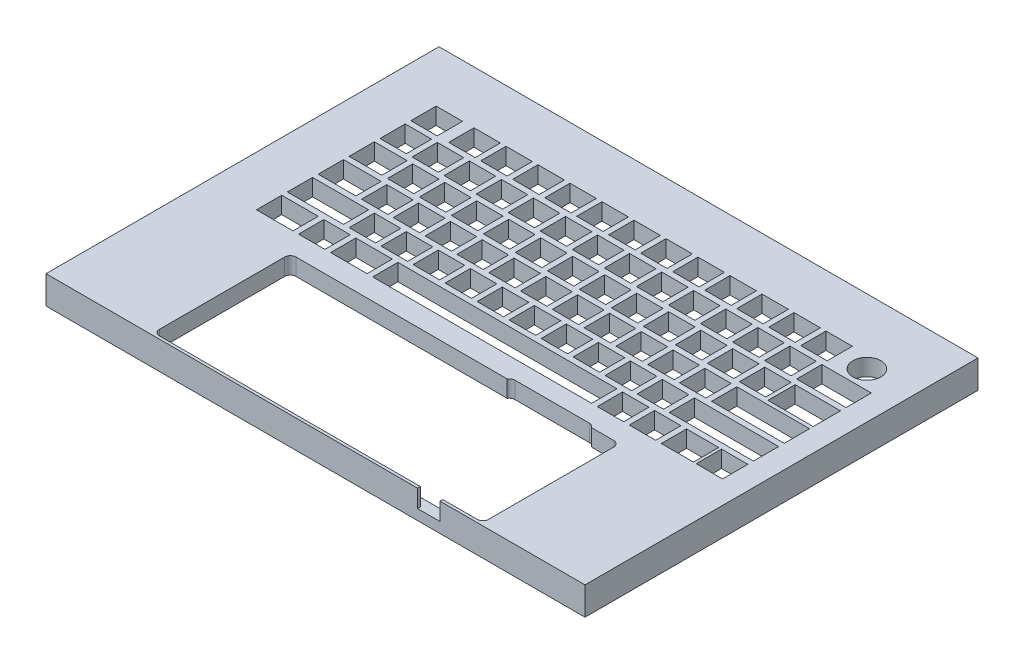
SolidWorks part; units mm, degrees
ref_plane "Front Plane" through (0, 0, 0) normal (0, 0, 1) x (1, 0, 0)
ref_plane "Top Plane" through (0, 0, 0) normal (0, 1, 0) x (1, 0, 0)
ref_plane "Right Plane" through (0, 0, 0) normal (1, 0, 0) x (0, 0, -1)
sketch "Sketch1" plane through (0, 0, 0) normal (0, 1, 0) x (1, 0, 0)
  line L0 (5.08, 5.08) -> (238.76, 5.08)
  line L1 (0, 0) -> (243.84, 0)
  line L2 (0, 0) -> (0, 177.8)
  line L3 (0, 177.8) -> (243.84, 177.8)
  line L4 (243.84, 0) -> (243.84, 177.8)
  line L5 (238.76, 5.08) -> (238.76, 172.72)
  line L6 (5.08, 172.72) -> (238.76, 172.72)
  line L7 (5.08, 5.08) -> (5.08, 172.72)
  dimension "D1" = 177.8
  dimension "D2" = 243.84
  dimension "D3" = 5.08
extrude "Boss-Extrude7" add sketch "Sketch1" along normal blind 12.7
sketch "Sketch6" plane through (0, 12.7, 0) normal (0, 1, 0) x (1, 0, 0)
  line L0 (5.08, 172.72) -> (5.08, 5.08)
  line L1 (5.08, 5.08) -> (238.76, 5.08)
  line L2 (238.76, 5.08) -> (238.76, 172.72)
  line L3 (238.76, 172.72) -> (5.08, 172.72)
extrude "Boss-Extrude8" add sketch "Sketch6" against normal blind 7.62
sketch "Sketch7" plane through (0, 12.7, 0) normal (0, 1, 0) x (1, 0, 0)
  line L0 (0, 0) -> (243.84, 0) construction
  line L1 (0, 177.8) -> (0, 0) construction
  line L2 (243.84, 0) -> (243.84, 177.8) construction
  line L3 (196.37, 1.27) -> (178.2581, 1.27)
  line L4 (47.47, 1.27) -> (47.47, 63.07)
  line L6 (196.37, 63.07) -> (196.37, 1.27)
  line L8 (47.47, 32.17) -> (0, 32.17) construction
  line L9 (196.37, 32.17) -> (243.84, 32.17) construction
  line L11 (168.0981, 0) -> (178.2581, 0)
  line L12 (178.2581, 0) -> (178.2581, 1.27)
  line L14 (157.9954, 1.27) -> (47.47, 1.27)
  line L15 (157.9954, 1.27) -> (168.0981, 1.27)
  line L16 (168.0981, 1.27) -> (168.0981, 0)
  line L18 (183.67, 64.34) -> (145.57, 64.34)
  line L20 (196.37, 63.07) -> (183.67, 63.07)
  line L21 (145.57, 63.07) -> (47.47, 63.07)
  line L22 (183.67, 63.07) -> (183.67, 64.34)
  line L23 (145.57, 63.07) -> (145.57, 64.34)
  dimension "D1" = 1.27
  dimension "D2" = 148.9
  dimension "D3" = 61.8
  dimension "D4" = 10.16
  dimension "D5" = 38.1
  dimension "D6" = 12.7
  dimension "D7" = 1.27
extrude "Cut-Extrude2" cut sketch "Sketch7" against normal blind 8 contours L4 L21 L23 L18 L22 L20 L6 L3 L12 L11 L16 L15 L14
fillet "Fillet1" radius 2.54 4 edges at (47.47, 8.89, -63.07) (47.47, 8.7, -1.27) (196.37, 8.7, -1.27) (196.37, 8.89, -63.07)
fillet "Fillet2" radius 2.54 2 edges at (145.57, 8.89, -64.34) (183.67, 8.89, -64.34)
sketch "Sketch8" plane through (0, 12.7, 0) normal (0, 1, 0) x (1, 0, 0)
  line L0 (50.5293, 86.591) -> (50.5293, 97.9956)
  line L1 (50.5293, 97.9956) -> (62.5181, 97.9956)
  line L2 (62.5181, 97.9956) -> (62.5181, 86.591)
  line L3 (62.5181, 86.591) -> (50.5293, 86.591)
  line L4 (76.9961, 86.591) -> (65.0073, 86.591)
  line L5 (65.0073, 86.591) -> (65.0073, 97.9956)
  line L6 (65.0073, 97.9956) -> (76.9961, 97.9956)
  line L7 (76.9961, 97.9956) -> (76.9961, 86.591)
  line L8 (91.4741, 86.591) -> (79.4853, 86.591)
  line L9 (79.4853, 86.591) -> (79.4853, 97.9956)
  line L10 (79.4853, 97.9956) -> (91.4741, 97.9956)
  line L11 (91.4741, 97.9956) -> (91.4741, 86.591)
  line L12 (105.9521, 86.591) -> (93.9633, 86.591)
  line L13 (93.9633, 86.591) -> (93.9633, 97.9956)
  line L14 (93.9633, 97.9956) -> (105.9521, 97.9956)
  line L15 (105.9521, 97.9956) -> (105.9521, 86.591)
  line L16 (120.4301, 86.591) -> (108.4413, 86.591)
  line L17 (108.4413, 86.591) -> (108.4413, 97.9956)
  line L18 (108.4413, 97.9956) -> (120.4301, 97.9956)
  line L19 (120.4301, 97.9956) -> (120.4301, 86.591)
  line L20 (134.9081, 86.591) -> (122.9193, 86.591)
  line L21 (122.9193, 86.591) -> (122.9193, 97.9956)
  line L22 (122.9193, 97.9956) -> (134.9081, 97.9956)
  line L23 (134.9081, 97.9956) -> (134.9081, 86.591)
  line L24 (149.3861, 86.591) -> (137.3973, 86.591)
  line L25 (137.3973, 86.591) -> (137.3973, 97.9956)
  line L26 (137.3973, 97.9956) -> (149.3861, 97.9956)
  line L27 (149.3861, 97.9956) -> (149.3861, 86.591)
  line L28 (163.8641, 86.591) -> (151.8753, 86.591)
  line L29 (151.8753, 86.591) -> (151.8753, 97.9956)
  line L30 (151.8753, 97.9956) -> (163.8641, 97.9956)
  line L31 (163.8641, 97.9956) -> (163.8641, 86.591)
  line L32 (178.3421, 86.591) -> (166.3533, 86.591)
  line L33 (166.3533, 86.591) -> (166.3533, 97.9956)
  line L34 (166.3533, 97.9956) -> (178.3421, 97.9956)
  line L35 (178.3421, 97.9956) -> (178.3421, 86.591)
  line L36 (192.8201, 86.591) -> (180.8313, 86.591)
  line L37 (180.8313, 86.591) -> (180.8313, 97.9956)
  line L38 (180.8313, 97.9956) -> (192.8201, 97.9956)
  line L39 (192.8201, 97.9956) -> (192.8201, 86.591)
  line L40 (120.4301, 92.2933) -> (122.9193, 92.2933) construction
  line L43 (120.4301, 92.2933) -> (0, 92.2933) construction
  line L44 (0, 177.8) -> (0, 0) construction
  line L45 (47.9893, 86.591) -> (22.5893, 86.591)
  line L46 (22.5893, 86.591) -> (22.5893, 97.9956)
  line L47 (22.5893, 97.9956) -> (47.9893, 97.9956)
  line L48 (47.9893, 97.9956) -> (47.9893, 86.591)
  line L55 (195.3601, 97.9956) -> (195.3601, 86.591)
  line L56 (195.3601, 86.591) -> (233.4601, 86.591)
  line L57 (233.4601, 86.591) -> (233.4601, 97.9956)
  line L58 (233.4601, 97.9956) -> (195.3601, 97.9956)
  line L59 (192.8201, 86.591) -> (195.3601, 86.591) construction
  line L60 (192.8201, 97.9956) -> (195.3601, 97.9956) construction
  line L61 (75.1673, 72.621) -> (75.1673, 84.051)
  line L62 (75.1673, 84.051) -> (174.2273, 84.051)
  line L63 (174.2273, 84.051) -> (174.2273, 72.621)
  line L64 (174.2273, 72.621) -> (75.1673, 72.621)
  line L65 (72.6273, 72.6364) -> (72.6273, 84.051)
  line L66 (72.6273, 84.051) -> (56.1173, 84.051)
  line L67 (56.1173, 84.051) -> (56.1173, 72.6364)
  line L68 (56.1173, 72.6364) -> (72.6273, 72.6364)
  line L69 (53.5773, 72.621) -> (53.5773, 84.051)
  line L70 (53.5773, 84.051) -> (41.6393, 84.051)
  line L71 (41.6393, 84.051) -> (41.6393, 72.621)
  line L72 (41.6393, 72.621) -> (53.5773, 72.621)
  line L73 (39.0993, 72.621) -> (39.0993, 84.051)
  line L74 (39.0993, 84.051) -> (22.5893, 84.051)
  line L75 (22.5893, 84.051) -> (22.5893, 72.621)
  line L76 (22.5893, 72.621) -> (39.0993, 72.621)
  line L78 (188.7052, 72.6364) -> (188.7052, 84.0664)
  line L79 (188.7052, 84.0664) -> (176.7672, 84.0664)
  line L80 (176.7672, 84.0664) -> (176.7672, 72.6364)
  line L81 (176.7672, 72.6364) -> (188.7052, 72.6364)
  line L96 (42.1943, 111.9656) -> (42.1943, 100.5356)
  line L97 (42.1943, 100.5356) -> (54.1323, 100.5356)
  line L98 (54.1323, 100.5356) -> (54.1323, 111.9656)
  line L99 (54.1323, 111.9656) -> (42.1943, 111.9656)
  line L100 (68.5217, 111.9656) -> (56.5837, 111.9656)
  line L101 (56.5837, 111.9656) -> (56.5837, 100.5356)
  line L102 (56.5837, 100.5356) -> (68.5217, 100.5356)
  line L103 (68.5217, 100.5356) -> (68.5217, 111.9656)
  line L104 (82.911, 111.9656) -> (70.973, 111.9656)
  line L105 (70.973, 111.9656) -> (70.973, 100.5356)
  line L106 (70.973, 100.5356) -> (82.911, 100.5356)
  line L107 (82.911, 100.5356) -> (82.911, 111.9656)
  line L108 (97.3003, 111.9656) -> (85.3623, 111.9656)
  line L109 (85.3623, 111.9656) -> (85.3623, 100.5356)
  line L110 (85.3623, 100.5356) -> (97.3003, 100.5356)
  line L111 (97.3003, 100.5356) -> (97.3003, 111.9656)
  line L112 (111.6896, 111.9656) -> (99.7516, 111.9656)
  line L113 (99.7516, 111.9656) -> (99.7516, 100.5356)
  line L114 (99.7516, 100.5356) -> (111.6896, 100.5356)
  line L115 (111.6896, 100.5356) -> (111.6896, 111.9656)
  line L116 (126.079, 111.9656) -> (114.141, 111.9656)
  line L117 (114.141, 111.9656) -> (114.141, 100.5356)
  line L118 (114.141, 100.5356) -> (126.079, 100.5356)
  line L119 (126.079, 100.5356) -> (126.079, 111.9656)
  line L120 (140.4683, 111.9656) -> (128.5303, 111.9656)
  line L121 (128.5303, 111.9656) -> (128.5303, 100.5356)
  line L122 (128.5303, 100.5356) -> (140.4683, 100.5356)
  line L123 (140.4683, 100.5356) -> (140.4683, 111.9656)
  line L124 (154.8576, 111.9656) -> (142.9196, 111.9656)
  line L125 (142.9196, 111.9656) -> (142.9196, 100.5356)
  line L126 (142.9196, 100.5356) -> (154.8576, 100.5356)
  line L127 (154.8576, 100.5356) -> (154.8576, 111.9656)
  line L128 (169.247, 111.9656) -> (157.309, 111.9656)
  line L129 (157.309, 111.9656) -> (157.309, 100.5356)
  line L130 (157.309, 100.5356) -> (169.247, 100.5356)
  line L131 (169.247, 100.5356) -> (169.247, 111.9656)
  line L132 (183.6363, 111.9656) -> (171.6983, 111.9656)
  line L133 (171.6983, 111.9656) -> (171.6983, 100.5356)
  line L134 (171.6983, 100.5356) -> (183.6363, 100.5356)
  line L135 (183.6363, 100.5356) -> (183.6363, 111.9656)
  line L136 (198.0256, 111.9656) -> (186.0876, 111.9656)
  line L137 (186.0876, 111.9656) -> (186.0876, 100.5356)
  line L138 (186.0876, 100.5356) -> (198.0256, 100.5356)
  line L139 (198.0256, 100.5356) -> (198.0256, 111.9656)
  line L140 (39.6543, 100.5356) -> (22.5893, 100.5356)
  line L141 (22.5893, 100.5356) -> (22.5893, 111.9656)
  line L142 (22.5893, 111.9656) -> (39.6543, 111.9656)
  line L143 (39.6543, 111.9656) -> (39.6543, 100.5356)
  line L144 (200.5656, 111.9656) -> (200.5656, 100.5356)
  line L145 (200.5656, 100.5356) -> (233.4601, 100.5356)
  line L146 (233.4601, 100.5356) -> (233.4601, 111.9656)
  line L147 (233.4601, 111.9656) -> (200.5656, 111.9656)
  line L156 (51.8757, 125.9592) -> (39.9377, 125.9592)
  line L157 (39.9377, 125.9592) -> (39.9377, 114.5056)
  line L158 (39.9377, 114.5056) -> (51.8757, 114.5056)
  line L159 (51.8757, 114.5056) -> (51.8757, 125.9592)
  line L196 (66.3537, 125.9592) -> (54.4157, 125.9592)
  line L197 (54.4157, 125.9592) -> (54.4157, 114.5056)
  line L198 (54.4157, 114.5056) -> (66.3537, 114.5056)
  line L199 (66.3537, 114.5056) -> (66.3537, 125.9592)
  line L200 (80.8317, 125.9592) -> (68.8937, 125.9592)
  line L201 (68.8937, 125.9592) -> (68.8937, 114.5056)
  line L202 (68.8937, 114.5056) -> (80.8317, 114.5056)
  line L203 (80.8317, 114.5056) -> (80.8317, 125.9592)
  line L204 (95.3097, 125.9592) -> (83.3717, 125.9592)
  line L205 (83.3717, 125.9592) -> (83.3717, 114.5056)
  line L206 (83.3717, 114.5056) -> (95.3097, 114.5056)
  line L207 (95.3097, 114.5056) -> (95.3097, 125.9592)
  line L208 (109.7877, 125.9592) -> (97.8497, 125.9592)
  line L209 (97.8497, 125.9592) -> (97.8497, 114.5056)
  line L210 (97.8497, 114.5056) -> (109.7877, 114.5056)
  line L211 (109.7877, 114.5056) -> (109.7877, 125.9592)
  line L212 (124.2657, 125.9592) -> (112.3277, 125.9592)
  line L213 (112.3277, 125.9592) -> (112.3277, 114.5056)
  line L214 (112.3277, 114.5056) -> (124.2657, 114.5056)
  line L215 (124.2657, 114.5056) -> (124.2657, 125.9592)
  line L216 (138.7437, 125.9592) -> (126.8057, 125.9592)
  line L217 (126.8057, 125.9592) -> (126.8057, 114.5056)
  line L218 (126.8057, 114.5056) -> (138.7437, 114.5056)
  line L219 (138.7437, 114.5056) -> (138.7437, 125.9592)
  line L220 (153.2217, 125.9592) -> (141.2837, 125.9592)
  line L221 (141.2837, 125.9592) -> (141.2837, 114.5056)
  line L222 (141.2837, 114.5056) -> (153.2217, 114.5056)
  line L223 (153.2217, 114.5056) -> (153.2217, 125.9592)
  line L224 (167.6997, 125.9592) -> (155.7617, 125.9592)
  line L225 (155.7617, 125.9592) -> (155.7617, 114.5056)
  line L226 (155.7617, 114.5056) -> (167.6997, 114.5056)
  line L227 (167.6997, 114.5056) -> (167.6997, 125.9592)
  line L228 (182.1777, 125.9592) -> (170.2397, 125.9592)
  line L229 (170.2397, 125.9592) -> (170.2397, 114.5056)
  line L230 (170.2397, 114.5056) -> (182.1777, 114.5056)
  line L231 (182.1777, 114.5056) -> (182.1777, 125.9592)
  line L232 (196.6557, 125.9592) -> (184.7177, 125.9592)
  line L233 (184.7177, 125.9592) -> (184.7177, 114.5056)
  line L234 (184.7177, 114.5056) -> (196.6557, 114.5056)
  line L235 (196.6557, 114.5056) -> (196.6557, 125.9592)
  line L236 (211.1337, 125.9592) -> (199.1957, 125.9592)
  line L237 (199.1957, 125.9592) -> (199.1957, 114.5056)
  line L238 (199.1957, 114.5056) -> (211.1337, 114.5056)
  line L239 (211.1337, 114.5056) -> (211.1337, 125.9592)
  line L240 (37.3977, 114.5056) -> (22.5893, 114.5056)
  line L241 (22.5893, 114.5056) -> (22.5893, 125.9592)
  line L242 (22.5893, 125.9592) -> (37.3977, 125.9592)
  line L243 (37.3977, 125.9592) -> (37.3977, 114.5056)
  line L244 (212.9454, 113.6508) -> (212.9454, 125.9592)
  line L245 (212.9454, 125.9592) -> (233.4601, 125.9592)
  line L246 (233.4601, 125.9592) -> (233.4601, 113.6508)
  line L247 (233.4601, 113.6508) -> (212.9454, 113.6508)
  line L248 (22.5893, 128.4992) -> (22.5893, 139.9292)
  line L249 (22.5893, 139.9292) -> (34.5273, 139.9292)
  line L250 (34.5273, 139.9292) -> (34.5273, 128.4992)
  line L251 (34.5273, 128.4992) -> (22.5893, 128.4992)
  line L252 (49.0288, 128.4992) -> (37.0908, 128.4992)
  line L253 (37.0908, 128.4992) -> (37.0908, 139.9292)
  line L254 (37.0908, 139.9292) -> (49.0288, 139.9292)
  line L255 (49.0288, 139.9292) -> (49.0288, 128.4992)
  line L256 (63.5303, 128.4992) -> (51.5923, 128.4992)
  line L257 (51.5923, 128.4992) -> (51.5923, 139.9292)
  line L258 (51.5923, 139.9292) -> (63.5303, 139.9292)
  line L259 (63.5303, 139.9292) -> (63.5303, 128.4992)
  line L260 (78.0318, 128.4992) -> (66.0938, 128.4992)
  line L261 (66.0938, 128.4992) -> (66.0938, 139.9292)
  line L262 (66.0938, 139.9292) -> (78.0318, 139.9292)
  line L263 (78.0318, 139.9292) -> (78.0318, 128.4992)
  line L264 (92.5334, 128.4992) -> (80.5954, 128.4992)
  line L265 (80.5954, 128.4992) -> (80.5954, 139.9292)
  line L266 (80.5954, 139.9292) -> (92.5334, 139.9292)
  line L267 (92.5334, 139.9292) -> (92.5334, 128.4992)
  line L268 (107.0349, 128.4992) -> (95.0969, 128.4992)
  line L269 (95.0969, 128.4992) -> (95.0969, 139.9292)
  line L270 (95.0969, 139.9292) -> (107.0349, 139.9292)
  line L271 (107.0349, 139.9292) -> (107.0349, 128.4992)
  line L272 (121.5364, 128.4992) -> (109.5984, 128.4992)
  line L273 (109.5984, 128.4992) -> (109.5984, 139.9292)
  line L274 (109.5984, 139.9292) -> (121.5364, 139.9292)
  line L275 (121.5364, 139.9292) -> (121.5364, 128.4992)
  line L276 (136.0379, 128.4992) -> (124.0999, 128.4992)
  line L277 (124.0999, 128.4992) -> (124.0999, 139.9292)
  line L278 (124.0999, 139.9292) -> (136.0379, 139.9292)
  line L279 (136.0379, 139.9292) -> (136.0379, 128.4992)
  line L280 (150.5395, 128.4992) -> (138.6015, 128.4992)
  line L281 (138.6015, 128.4992) -> (138.6015, 139.9292)
  line L282 (138.6015, 139.9292) -> (150.5395, 139.9292)
  line L283 (150.5395, 139.9292) -> (150.5395, 128.4992)
  line L284 (165.041, 128.4992) -> (153.103, 128.4992)
  line L285 (153.103, 128.4992) -> (153.103, 139.9292)
  line L286 (153.103, 139.9292) -> (165.041, 139.9292)
  line L287 (165.041, 139.9292) -> (165.041, 128.4992)
  line L288 (179.5425, 128.4992) -> (167.6045, 128.4992)
  line L289 (167.6045, 128.4992) -> (167.6045, 139.9292)
  line L290 (167.6045, 139.9292) -> (179.5425, 139.9292)
  line L291 (179.5425, 139.9292) -> (179.5425, 128.4992)
  line L292 (194.044, 128.4992) -> (182.106, 128.4992)
  line L293 (182.106, 128.4992) -> (182.106, 139.9292)
  line L294 (182.106, 139.9292) -> (194.044, 139.9292)
  line L295 (194.044, 139.9292) -> (194.044, 128.4992)
  line L296 (208.5455, 128.4992) -> (196.6075, 128.4992)
  line L297 (196.6075, 128.4992) -> (196.6075, 139.9292)
  line L298 (196.6075, 139.9292) -> (208.5455, 139.9292)
  line L299 (208.5455, 139.9292) -> (208.5455, 128.4992)
  line L300 (211.0855, 128.4992) -> (233.4601, 128.4992)
  line L301 (233.4601, 128.4992) -> (233.4601, 139.9292)
  line L302 (233.4601, 139.9292) -> (211.0855, 139.9292)
  line L303 (211.0855, 139.9292) -> (211.0855, 128.4992)
  line L304 (221.5221, 72.621) -> (221.5221, 84.0664)
  line L305 (221.5221, 84.0664) -> (233.4601, 84.0664)
  line L306 (233.4601, 84.0664) -> (233.4601, 72.621)
  line L307 (233.4601, 72.621) -> (221.5221, 72.621)
  line L308 (191.2452, 72.621) -> (191.2452, 84.0664)
  line L309 (191.2452, 84.0664) -> (203.1832, 84.0664)
  line L310 (203.1832, 84.0664) -> (203.1832, 72.621)
  line L311 (203.1832, 72.621) -> (191.2452, 72.621)
  line L318 (205.7232, 84.0664) -> (205.7232, 72.621)
  line L319 (205.7232, 72.621) -> (220.2767, 72.621)
  line L320 (220.2767, 72.621) -> (220.2767, 84.0664)
  line L321 (220.2767, 84.0664) -> (205.7232, 84.0664)
  line L322 (22.5893, 142.4692) -> (22.5893, 153.8992)
  line L323 (22.5893, 153.8992) -> (34.5273, 153.8992)
  line L324 (34.5273, 153.8992) -> (34.5273, 142.4692)
  line L325 (34.5273, 142.4692) -> (22.5893, 142.4692)
  line L326 (39.6543, 142.5358) -> (39.6543, 153.9658)
  line L327 (39.6543, 153.9658) -> (51.5923, 153.9658)
  line L328 (51.5923, 153.9658) -> (51.5923, 142.5358)
  line L329 (51.5923, 142.5358) -> (39.6543, 142.5358)
  line L330 (66.0703, 142.5358) -> (54.1323, 142.5358)
  line L331 (54.1323, 142.5358) -> (54.1323, 153.9658)
  line L332 (54.1323, 153.9658) -> (66.0703, 153.9658)
  line L333 (66.0703, 153.9658) -> (66.0703, 142.5358)
  line L334 (80.5483, 142.5358) -> (68.6103, 142.5358)
  line L335 (68.6103, 142.5358) -> (68.6103, 153.9658)
  line L336 (68.6103, 153.9658) -> (80.5483, 153.9658)
  line L337 (80.5483, 153.9658) -> (80.5483, 142.5358)
  line L338 (95.0263, 142.5358) -> (83.0883, 142.5358)
  line L339 (83.0883, 142.5358) -> (83.0883, 153.9658)
  line L340 (83.0883, 153.9658) -> (95.0263, 153.9658)
  line L341 (95.0263, 153.9658) -> (95.0263, 142.5358)
  line L342 (109.5043, 142.5358) -> (97.5663, 142.5358)
  line L343 (97.5663, 142.5358) -> (97.5663, 153.9658)
  line L344 (97.5663, 153.9658) -> (109.5043, 153.9658)
  line L345 (109.5043, 153.9658) -> (109.5043, 142.5358)
  line L346 (123.9823, 142.5358) -> (112.0443, 142.5358)
  line L347 (112.0443, 142.5358) -> (112.0443, 153.9658)
  line L348 (112.0443, 153.9658) -> (123.9823, 153.9658)
  line L349 (123.9823, 153.9658) -> (123.9823, 142.5358)
  line L350 (138.4603, 142.5358) -> (126.5223, 142.5358)
  line L351 (126.5223, 142.5358) -> (126.5223, 153.9658)
  line L352 (126.5223, 153.9658) -> (138.4603, 153.9658)
  line L353 (138.4603, 153.9658) -> (138.4603, 142.5358)
  line L354 (152.9383, 142.5358) -> (141.0003, 142.5358)
  line L355 (141.0003, 142.5358) -> (141.0003, 153.9658)
  line L356 (141.0003, 153.9658) -> (152.9383, 153.9658)
  line L357 (152.9383, 153.9658) -> (152.9383, 142.5358)
  line L358 (167.4163, 142.5358) -> (155.4783, 142.5358)
  line L359 (155.4783, 142.5358) -> (155.4783, 153.9658)
  line L360 (155.4783, 153.9658) -> (167.4163, 153.9658)
  line L361 (167.4163, 153.9658) -> (167.4163, 142.5358)
  line L362 (181.8943, 142.5358) -> (169.9563, 142.5358)
  line L363 (169.9563, 142.5358) -> (169.9563, 153.9658)
  line L364 (169.9563, 153.9658) -> (181.8943, 153.9658)
  line L365 (181.8943, 153.9658) -> (181.8943, 142.5358)
  line L366 (196.3723, 142.5358) -> (184.4343, 142.5358)
  line L367 (184.4343, 142.5358) -> (184.4343, 153.9658)
  line L368 (184.4343, 153.9658) -> (196.3723, 153.9658)
  line L369 (196.3723, 153.9658) -> (196.3723, 142.5358)
  line L370 (210.8503, 142.5358) -> (198.9123, 142.5358)
  line L371 (198.9123, 142.5358) -> (198.9123, 153.9658)
  line L372 (198.9123, 153.9658) -> (210.8503, 153.9658)
  line L373 (210.8503, 153.9658) -> (210.8503, 142.5358)
  line L374 (51.5923, 142.5358) -> (66.0703, 142.5358) construction
  circle A0 centre (222.9667, 148.4094) radius 6.35
  dimension "D1" = 11.9888
  dimension "D2" = 11.4046
  dimension "D4" = 25.4
  dimension "D5" = 2.4892
  dimension "D6" = 2.54
  dimension "D7" = 38.1
  dimension "D8" = 2.54
  dimension "D9" = 99.06
  dimension "D10" = 11.43
  dimension "D11" = 11.43
  dimension "D12" = 2.54
  dimension "D13" = 16.51
  dimension "D14" = 11.938
  dimension "D15" = 16.51
  dimension "D16" = 2.54
  dimension "D17" = 2.54
  dimension "D18" = 2.54
  dimension "D19" = 11.938
  dimension "D20" = 11.4454
  dimension "D21" = 11.43
  dimension "D22" = 2.54
  dimension "D23" = 11.938
  dimension "D24" = 11.938
  dimension "D25" = 2.54
  dimension "D26" = 11.43
  dimension "D27" = 1.2454
  dimension "D28" = 11.938
  dimension "D29" = 11.43
  dimension "D30" = 2.54
  dimension "D32" = 2.54
  dimension "D33" = 2.54
  dimension "D34" = 2.54
  dimension "D35" = 12
  dimension "D36" = 2.54
  dimension "D37" = 2.54
  dimension "D38" = 11.938
  dimension "D39" = 11.43
  dimension "D41" = 2.54
  dimension "D42" = 2.54
  dimension "D43" = 11.938
  dimension "D44" = 2.54
  dimension "D45" = 11.43
  dimension "D46" = 12
  dimension "D47" = 14.478
  dimension "D48" = 2.5635
  dimension "D3" = 10
  dimension "D31" = 11
  dimension "D40" = 13
extrude "Cut-Extrude3" cut sketch "Sketch8" against normal up to next (7.62 mm away) contours L302 L303 L300 L301 | L247 L246 L245 L244 | L146 L147 L144 L145 | L57 L58 L55 L56 | L307 L306 L305 L304 | L320 L321 L318 L319 | L311 L310 L309 L308 | L80 L81 L78 L79 | L39 L38 L37 L36 | L134 L135 L132 L133 | L138 L139 L136 L137 | L234 L235 L232 L233 | L238 L239 L236 L237 | L373 L372 L371 L370 | L369 L368 L367 L366 | L295 L294 L293 L292 | L365 L364 L363 L362 | L291 L290 L289 L288 | L230 L231 L228 L229 | L64 L63 L62 L61 | L75 L76 L73 L74 | L71 L72 L69 L70 | L67 L68 L65 L66 | L48 L47 L46 L45 | L143 L142 L141 L140 | L98 L99 L96 L97 | L102 L103 L100 L101 | L106 L107 L104 L105 | L110 L111 L108 L109 | L11 L10 L9 L8 | L3 L2 L1 L0 | L7 L6 L5 L4 | L114 L115 L112 L113 | L15 L14 L13 L12 | L19 L18 L17 L16 | L23 L22 L21 L20 | L118 L119 L116 L117 | L122 L123 L120 L121 | L27 L26 L25 L24 | L31 L30 L29 L28 | L126 L127 L124 L125 | L130 L131 L128 L129 | L226 L227 L224 L225 | L222 L223 L220 L221 | L218 L219 L216 L217 | L214 L215 L212 L213 | L210 L211 L208 L209 | L206 L207 L204 L205 | L202 L203 L200 L201 | L198 L199 L196 L197 | L158 L159 L156 L157 | L243 L242 L241 L240 | L251 L250 L249 L248 | L325 L324 L323 L322 | L329 L328 L327 L326 | L255 L254 L253 L252 | L259 L258 L257 L256 | L333 L332 L331 L330 | L337 L336 L335 L334 | L263 L262 L261 L260 | L267 L266 L265 L264 | L341 L340 L339 L338 | L345 L344 L343 L342 | L271 L270 L269 L268 | L275 L274 L273 L272 | L349 L348 L347 L346 | L353 L352 L351 L350 | L279 L278 L277 L276 | L283 L282 L281 L280 | L357 L356 L355 L354 | L361 L360 L359 L358 | L287 L286 L285 L284 | A0 | L34 L35 L32 L33 | L298 L299 L296 L297 region at (56.5237, 12.7, -92.2933) region at (71.0017, 12.7, -92.2933) region at (85.4797, 12.7, -92.2933) region at (99.9577, 12.7, -92.2933) region at (114.4357, 12.7, -92.2933) region at (128.9137, 12.7, -92.2933) region at (143.3917, 12.7, -92.2933) region at (157.8697, 12.7, -92.2933) region at (186.8257, 12.7, -92.2933) region at (35.2893, 12.7, -92.2933) region at (214.4101, 12.7, -92.2933) region at (124.6973, 12.7, -78.336) region at (64.3723, 12.7, -78.3437) region at (47.6083, 12.7, -78.336) region at (30.8443, 12.7, -78.336) region at (182.7362, 12.7, -78.3514) region at (48.1633, 12.7, -106.2506) region at (62.5527, 12.7, -106.2506) region at (76.942, 12.7, -106.2506) region at (91.3313, 12.7, -106.2506) region at (105.7206, 12.7, -106.2506) region at (120.11, 12.7, -106.2506) region at (134.4993, 12.7, -106.2506) region at (148.8886, 12.7, -106.2506) region at (163.278, 12.7, -106.2506) region at (177.6673, 12.7, -106.2506) region at (192.0566, 12.7, -106.2506) region at (31.1218, 12.7, -106.2506) region at (217.0128, 12.7, -106.2506) region at (45.9067, 12.7, -120.2324) region at (60.3847, 12.7, -120.2324) region at (74.8627, 12.7, -120.2324) region at (89.3407, 12.7, -120.2324) region at (103.8187, 12.7, -120.2324) region at (118.2967, 12.7, -120.2324) region at (132.7747, 12.7, -120.2324) region at (147.2527, 12.7, -120.2324) region at (161.7307, 12.7, -120.2324) region at (176.2087, 12.7, -120.2324) region at (190.6867, 12.7, -120.2324) region at (205.1647, 12.7, -120.2324) region at (29.9935, 12.7, -120.2324) region at (223.2027, 12.7, -119.805) region at (28.5583, 12.7, -134.2142) region at (43.0598, 12.7, -134.2142) region at (57.5613, 12.7, -134.2142) region at (72.0628, 12.7, -134.2142) region at (86.5644, 12.7, -134.2142) region at (101.0659, 12.7, -134.2142) region at (115.5674, 12.7, -134.2142) region at (130.0689, 12.7, -134.2142) region at (144.5705, 12.7, -134.2142) region at (159.072, 12.7, -134.2142) region at (173.5735, 12.7, -134.2142) region at (188.075, 12.7, -134.2142) region at (222.2728, 12.7, -134.2142) region at (227.4911, 12.7, -78.3437) region at (197.2142, 12.7, -78.3437) region at (213, 12.7, -78.3437) region at (28.5583, 12.7, -148.1842)
sketch "Sketch10" plane through (0, 5.08, 0) normal (0, -1, 0) x (1, 0, 0)
  line L0 (50.01, -63.07) -> (47.47, -63.07) construction
  line L1 (47.47, -63.07) -> (47.47, -60.53) construction
  arc A0 (47.47, -60.53) -> (50.01, -63.07) centre (50.01, -60.53) ccw construction
  circle A1 centre (47.47, -63.07) radius 0.7937
  dimension "D1" = 1.5875
sketch "Sketch12" plane through (0, 0, -5.08) normal (0, 0, -1) x (-1, 0, 0)
  line L0 (-47.47, 4.7) -> (-47.47, 0) construction
  line L1 (-5.08, 0) -> (-238.76, 0) construction
sketch "Sketch13" plane through (0, 0, 0) normal (0, -1, 0) x (1, 0, 0)
  line L0 (47.47, -5.08) -> (47.47, 0) construction
  line L1 (0, 0) -> (243.84, 0) construction
  line L4 (196.37, -60.53) -> (196.37, -72.621) construction
  line L5 (191.2452, -72.621) -> (203.1832, -72.621) construction
  line L6 (196.37, -5.08) -> (196.37, 0) construction
  circle A2 centre (47.47, -66.04) radius 0.7937
  circle A3 centre (47.47, -2.54) radius 0.762
  circle A4 centre (81.0054, -36.7913) radius 0.7937
  circle A6 centre (110.97, -2.54) radius 0.762
  circle A7 centre (110.97, -66.04) radius 0.762
  circle A8 centre (196.37, -66.04) radius 0.762
  circle A9 centre (132.87, -66.04) radius 0.762
  circle A10 centre (132.87, -2.54) radius 0.762
  circle A11 centre (196.37, -2.54) radius 0.762
  point P31 (0, 0)
  point P32 (0, 0)
  point P33 (0, 0)
  point P34 (0, 0)
  point P35 (0, 0)
  dimension "D1" = 1.5875
  dimension "D3" = 63.5
  dimension "D2" = 1.524
  dimension "D4" = 1.524
  dimension "D5" = 1.524
  dimension "D8" = 1.524
  dimension "D9" = 1.524
  dimension "D11" = 1.524
  dimension "D12" = 1.524
  dimension "D6" = 63.5
  dimension "D7" = 63.5
  dimension "D10" = 63.5
  dimension "D13" = 63.5
